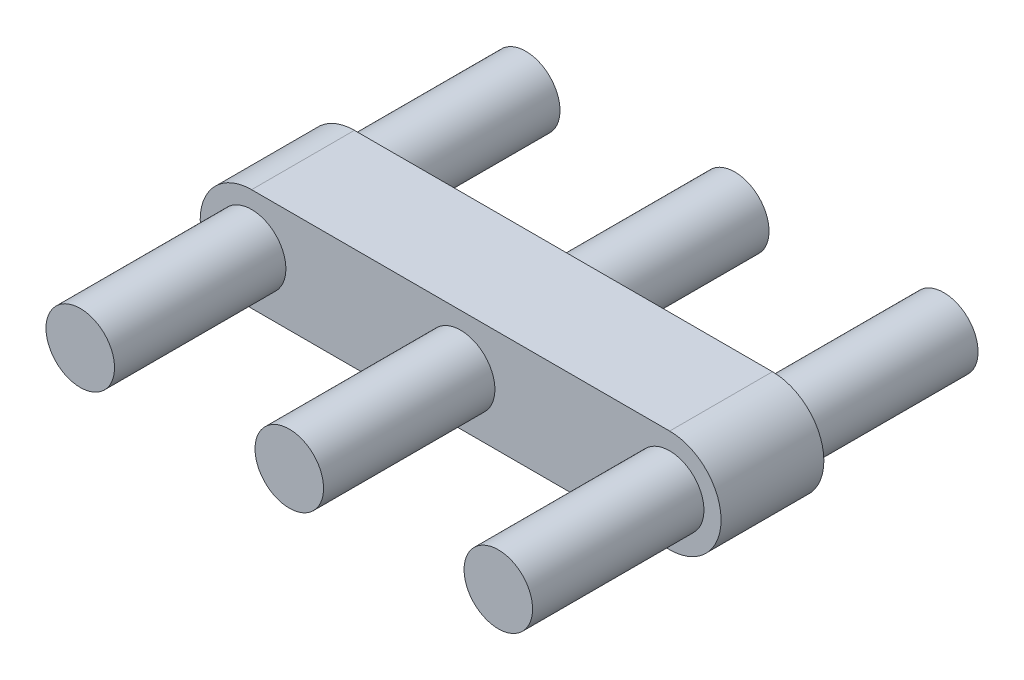
SolidWorks part; units mm, degrees
ref_plane "Front Plane" through (0, 0, 0) normal (0, 0, 1) x (1, 0, 0)
ref_plane "Top Plane" through (0, 0, 0) normal (0, 1, 0) x (1, 0, 0)
ref_plane "Right Plane" through (0, 0, 0) normal (1, 0, 0) x (0, 0, -1)
sketch "Sketch1" plane through (0, 0, 0) normal (0, 0, 1) x (1, 0, 0)
  line L0 (6.1, 0) -> (-6.1, 0) construction
  line L1 (6.1, -1.5) -> (-6.1, -1.5)
  line L2 (6.1, 1.5) -> (-6.1, 1.5)
  arc A0 (6.1, -1.5) -> (6.1, 1.5) centre (6.1, 0) ccw
  arc A1 (-6.1, 1.5) -> (-6.1, -1.5) centre (-6.1, 0) ccw
  circle A2 centre (-6.1, 0) radius 1
  circle A3 centre (6.1, 0) radius 1
  circle A4 centre (0, 0) radius 1
  point P2 (0, 0)
  dimension "D2" = 1.5
  dimension "D3" = 2
  dimension "D1" = 12.2
extrude "Boss-Extrude1" add sketch "Sketch1" along normal mid plane 3 contours L2 A1 L1 A0 A3 A2 | A2 | A3 region at (0, -1.3451, 0) region at (-6.1, 0, 0)
extrude "Boss-Extrude2" add sketch "Sketch1<3>" along normal mid plane 13 contours A2 | A4 | A3
sketch "Sketch1<3>" plane through (0, 0, 0) normal (0, 0, 1) x (1, 0, 0) same geometry as "Sketch1"
ref_plane "Plane1" through (0, 0, 0) normal (0, 0, 1) x (1, 0, 0)
ref_plane "Plane2" through (0, 0, 0) normal (1, 0, 0) x (0, 0, -1)
